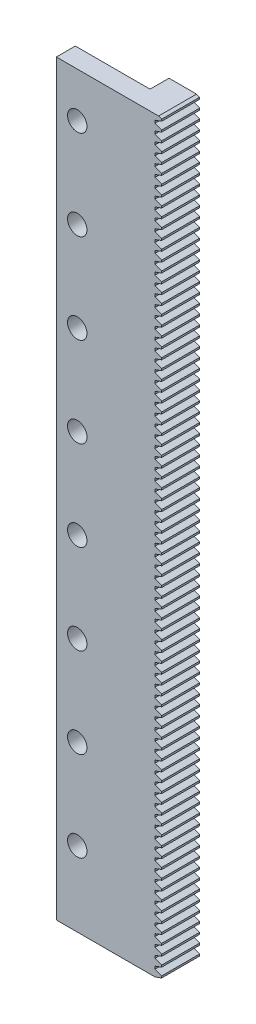
SolidWorks part; units mm, degrees
ref_plane "Front Plane" through (0, 0, 0) normal (0, 0, 1) x (1, 0, 0)
ref_plane "Top Plane" through (0, 0, 0) normal (0, 1, 0) x (1, 0, 0)
ref_plane "Right Plane" through (0, 0, 0) normal (1, 0, 0) x (0, 0, -1)
sketch "Sketch2" plane through (0, 0, 0) normal (0, 0, 1) x (1, 0, 0)
  line L0 (0, -62.5) -> (0, 62.5) construction
  line L1 (-3.5, -62.5) -> (3.5, -62.5) construction
  line L2 (-3.5, -62.5) -> (-3.5, 62.5) construction
  line L3 (-3.5, 62.5) -> (3.5, 62.5) construction
  line L4 (3.5, -62.5) -> (3.5, 62.5) construction
  line L5 (-3.5, -62.5) -> (3.5, 62.5) construction
  line L6 (-3.5, 62.5) -> (3.5, -62.5) construction
  line L202 (3.5, -62.5) -> (-3.5, -62.5)
  line L203 (-3.5, -62.5) -> (-3.5, 62.5)
  line L204 (-3.5, 62.5) -> (13.6024, 62.5)
  line L591 (3.5, -62.5) -> (8, -62.5)
  line L592 (-8, -15) -> (8, -15) construction
  line L593 (-8, -15) -> (-8, 15) construction
  line L594 (-8, 15) -> (8, 15) construction
  line L595 (8, -15) -> (8, 15) construction
  line L596 (-8, -15) -> (8, 15) construction
  line L597 (-8, 15) -> (8, -15) construction
  line L598 (8, -62.5) -> (13, -62.5)
  line L600 (13, -62.5) -> (14.125, -62.0905)
  line L601 (14.125, -62.0905) -> (14.125, -61.7831)
  line L602 (14.125, -61.7831) -> (13, -61.3736)
  line L603 (13, -61.3736) -> (13, -60.9292)
  line L604 (13, -60.9292) -> (14.125, -60.5197)
  line L605 (14.125, -60.5197) -> (14.125, -60.2123)
  line L606 (14.125, -60.2123) -> (13, -59.8028)
  line L607 (13, -59.8028) -> (13, -59.3584)
  line L608 (13, -59.3584) -> (14.125, -58.9489)
  line L609 (14.125, -58.9489) -> (14.125, -58.6415)
  line L610 (14.125, -58.6415) -> (13, -58.232)
  line L611 (13, -58.232) -> (13, -57.7876)
  line L612 (13, -57.7876) -> (14.125, -57.3781)
  line L613 (14.125, -57.3781) -> (14.125, -57.0707)
  line L614 (14.125, -57.0707) -> (13, -56.6613)
  line L615 (13, -56.6613) -> (13, -56.2168)
  line L616 (13, -56.2168) -> (14.125, -55.8073)
  line L617 (14.125, -55.8073) -> (14.125, -55.4999)
  line L618 (14.125, -55.4999) -> (13, -55.0905)
  line L619 (13, -55.0905) -> (13, -54.646)
  line L620 (13, -54.646) -> (14.125, -54.2366)
  line L621 (14.125, -54.2366) -> (14.125, -53.9291)
  line L622 (14.125, -53.9291) -> (13, -53.5197)
  line L623 (13, -53.5197) -> (13, -53.0752)
  line L624 (13, -53.0752) -> (14.125, -52.6658)
  line L625 (14.125, -52.6658) -> (14.125, -52.3583)
  line L626 (14.125, -52.3583) -> (13, -51.9489)
  line L627 (13, -51.9489) -> (13, -51.5044)
  line L628 (13, -51.5044) -> (14.125, -51.095)
  line L629 (14.125, -51.095) -> (14.125, -50.7875)
  line L630 (14.125, -50.7875) -> (13, -50.3781)
  line L631 (13, -50.3781) -> (13, -49.9336)
  line L632 (13, -49.9336) -> (14.125, -49.5242)
  line L633 (14.125, -49.5242) -> (14.125, -49.2167)
  line L634 (14.125, -49.2167) -> (13, -48.8073)
  line L635 (13, -48.8073) -> (13, -48.3628)
  line L636 (13, -48.3628) -> (14.125, -47.9534)
  line L637 (14.125, -47.9534) -> (14.125, -47.6459)
  line L638 (14.125, -47.6459) -> (13, -47.2365)
  line L639 (13, -47.2365) -> (13, -46.792)
  line L640 (13, -46.792) -> (14.125, -46.3826)
  line L641 (14.125, -46.3826) -> (14.125, -46.0751)
  line L642 (14.125, -46.0751) -> (13, -45.6657)
  line L643 (13, -45.6657) -> (13, -45.2212)
  line L644 (13, -45.2212) -> (14.125, -44.8118)
  line L645 (14.125, -44.8118) -> (14.125, -44.5043)
  line L646 (14.125, -44.5043) -> (13, -44.0949)
  line L647 (13, -44.0949) -> (13, -43.6504)
  line L648 (13, -43.6504) -> (14.125, -43.241)
  line L649 (14.125, -43.241) -> (14.125, -42.9335)
  line L650 (14.125, -42.9335) -> (13, -42.5241)
  line L651 (13, -42.5241) -> (13, -42.0796)
  line L652 (13, -42.0796) -> (14.125, -41.6702)
  line L653 (14.125, -41.6702) -> (14.125, -41.3628)
  line L654 (14.125, -41.3628) -> (13, -40.9533)
  line L655 (13, -40.9533) -> (13, -40.5089)
  line L656 (13, -40.5089) -> (14.125, -40.0994)
  line L657 (14.125, -40.0994) -> (14.125, -39.792)
  line L658 (14.125, -39.792) -> (13, -39.3825)
  line L659 (13, -39.3825) -> (13, -38.9381)
  line L660 (13, -38.9381) -> (14.125, -38.5286)
  line L661 (14.125, -38.5286) -> (14.125, -38.2212)
  line L662 (14.125, -38.2212) -> (13, -37.8117)
  line L663 (13, -37.8117) -> (13, -37.3673)
  line L664 (13, -37.3673) -> (14.125, -36.9578)
  line L665 (14.125, -36.9578) -> (14.125, -36.6504)
  line L666 (14.125, -36.6504) -> (13, -36.2409)
  line L667 (13, -36.2409) -> (13, -35.7965)
  line L668 (13, -35.7965) -> (14.125, -35.387)
  line L669 (14.125, -35.387) -> (14.125, -35.0796)
  line L670 (14.125, -35.0796) -> (13, -34.6701)
  line L671 (13, -34.6701) -> (13, -34.2257)
  line L672 (13, -34.2257) -> (14.125, -33.8162)
  line L673 (14.125, -33.8162) -> (14.125, -33.5088)
  line L674 (14.125, -33.5088) -> (13, -33.0993)
  line L675 (13, -33.0993) -> (13, -32.6549)
  line L676 (13, -32.6549) -> (14.125, -32.2454)
  line L677 (14.125, -32.2454) -> (14.125, -31.938)
  line L678 (14.125, -31.938) -> (13, -31.5285)
  line L679 (13, -31.5285) -> (13, -31.0841)
  line L680 (13, -31.0841) -> (14.125, -30.6746)
  line L681 (14.125, -30.6746) -> (14.125, -30.3672)
  line L682 (14.125, -30.3672) -> (13, -29.9577)
  line L683 (13, -29.9577) -> (13, -29.5133)
  line L684 (13, -29.5133) -> (14.125, -29.1038)
  line L685 (14.125, -29.1038) -> (14.125, -28.7964)
  line L686 (14.125, -28.7964) -> (13, -28.3869)
  line L687 (13, -28.3869) -> (13, -27.9425)
  line L688 (13, -27.9425) -> (14.125, -27.533)
  line L689 (14.125, -27.533) -> (14.125, -27.2256)
  line L690 (14.125, -27.2256) -> (13, -26.8161)
  line L691 (13, -26.8161) -> (13, -26.3717)
  line L692 (13, -26.3717) -> (14.125, -25.9622)
  line L693 (14.125, -25.9622) -> (14.125, -25.6548)
  line L694 (14.125, -25.6548) -> (13, -25.2453)
  line L695 (13, -25.2453) -> (13, -24.8009)
  line L696 (13, -24.8009) -> (14.125, -24.3914)
  line L697 (14.125, -24.3914) -> (14.125, -24.084)
  line L698 (14.125, -24.084) -> (13, -23.6745)
  line L699 (13, -23.6745) -> (13, -23.2301)
  line L700 (13, -23.2301) -> (14.125, -22.8206)
  line L701 (14.125, -22.8206) -> (14.125, -22.5132)
  line L702 (14.125, -22.5132) -> (13, -22.1037)
  line L703 (13, -22.1037) -> (13, -21.6593)
  line L704 (13, -21.6593) -> (14.125, -21.2498)
  line L705 (14.125, -21.2498) -> (14.125, -20.9424)
  line L706 (14.125, -20.9424) -> (13, -20.5329)
  line L707 (13, -20.5329) -> (13, -20.0885)
  line L708 (13, -20.0885) -> (14.125, -19.679)
  line L709 (14.125, -19.679) -> (14.125, -19.3716)
  line L710 (14.125, -19.3716) -> (13, -18.9621)
  line L711 (13, -18.9621) -> (13, -18.5177)
  line L712 (13, -18.5177) -> (14.125, -18.1082)
  line L713 (14.125, -18.1082) -> (14.125, -17.8008)
  line L714 (14.125, -17.8008) -> (13, -17.3913)
  line L715 (13, -17.3913) -> (13, -16.9469)
  line L716 (13, -16.9469) -> (14.125, -16.5374)
  line L717 (14.125, -16.5374) -> (14.125, -16.23)
  line L718 (14.125, -16.23) -> (13, -15.8205)
  line L719 (13, -15.8205) -> (13, -15.3761)
  line L720 (13, -15.3761) -> (14.125, -14.9666)
  line L721 (14.125, -14.9666) -> (14.125, -14.6592)
  line L722 (14.125, -14.6592) -> (13, -14.2497)
  line L723 (13, -14.2497) -> (13, -13.8053)
  line L724 (13, -13.8053) -> (14.125, -13.3958)
  line L725 (14.125, -13.3958) -> (14.125, -13.0884)
  line L726 (14.125, -13.0884) -> (13, -12.679)
  line L727 (13, -12.679) -> (13, -12.2345)
  line L728 (13, -12.2345) -> (14.125, -11.8251)
  line L729 (14.125, -11.8251) -> (14.125, -11.5176)
  line L730 (14.125, -11.5176) -> (13, -11.1082)
  line L731 (13, -11.1082) -> (13, -10.6637)
  line L732 (13, -10.6637) -> (14.125, -10.2543)
  line L733 (14.125, -10.2543) -> (14.125, -9.9468)
  line L734 (14.125, -9.9468) -> (13, -9.5374)
  line L735 (13, -9.5374) -> (13, -9.0929)
  line L736 (13, -9.0929) -> (14.125, -8.6835)
  line L737 (14.125, -8.6835) -> (14.125, -8.376)
  line L738 (14.125, -8.376) -> (13, -7.9666)
  line L739 (13, -7.9666) -> (13, -7.5221)
  line L740 (13, -7.5221) -> (14.125, -7.1127)
  line L741 (14.125, -7.1127) -> (14.125, -6.8052)
  line L742 (14.125, -6.8052) -> (13, -6.3958)
  line L743 (13, -6.3958) -> (13, -5.9513)
  line L744 (13, -5.9513) -> (14.125, -5.5419)
  line L745 (14.125, -5.5419) -> (14.125, -5.2344)
  line L746 (14.125, -5.2344) -> (13, -4.825)
  line L747 (13, -4.825) -> (13, -4.3805)
  line L748 (13, -4.3805) -> (14.125, -3.9711)
  line L749 (14.125, -3.9711) -> (14.125, -3.6636)
  line L750 (14.125, -3.6636) -> (13, -3.2542)
  line L751 (13, -3.2542) -> (13, -2.8097)
  line L752 (13, -2.8097) -> (14.125, -2.4003)
  line L753 (14.125, -2.4003) -> (14.125, -2.0928)
  line L754 (14.125, -2.0928) -> (13, -1.6834)
  line L755 (13, -1.6834) -> (13, -1.2389)
  line L756 (13, -1.2389) -> (14.125, -0.8295)
  line L757 (14.125, -0.8295) -> (14.125, -0.522)
  line L758 (14.125, -0.522) -> (13, -0.1126)
  line L759 (13, -0.1126) -> (13, 0.3319)
  line L760 (13, 0.3319) -> (14.125, 0.7413)
  line L761 (14.125, 0.7413) -> (14.125, 1.0487)
  line L762 (14.125, 1.0487) -> (13, 1.4582)
  line L763 (13, 1.4582) -> (13, 1.9026)
  line L764 (13, 1.9026) -> (14.125, 2.3121)
  line L765 (14.125, 2.3121) -> (14.125, 2.6195)
  line L766 (14.125, 2.6195) -> (13, 3.029)
  line L767 (13, 3.029) -> (13, 3.4734)
  line L768 (13, 3.4734) -> (14.125, 3.8829)
  line L769 (14.125, 3.8829) -> (14.125, 4.1903)
  line L770 (14.125, 4.1903) -> (13, 4.5998)
  line L771 (13, 4.5998) -> (13, 5.0442)
  line L772 (13, 5.0442) -> (14.125, 5.4537)
  line L773 (14.125, 5.4537) -> (14.125, 5.7611)
  line L774 (14.125, 5.7611) -> (13, 6.1706)
  line L775 (13, 6.1706) -> (13, 6.615)
  line L776 (13, 6.615) -> (14.125, 7.0245)
  line L777 (14.125, 7.0245) -> (14.125, 7.3319)
  line L778 (14.125, 7.3319) -> (13, 7.7414)
  line L779 (13, 7.7414) -> (13, 8.1858)
  line L780 (13, 8.1858) -> (14.125, 8.5953)
  line L781 (14.125, 8.5953) -> (14.125, 8.9027)
  line L782 (14.125, 8.9027) -> (13, 9.3122)
  line L783 (13, 9.3122) -> (13, 9.7566)
  line L784 (13, 9.7566) -> (14.125, 10.1661)
  line L785 (14.125, 10.1661) -> (14.125, 10.4735)
  line L786 (14.125, 10.4735) -> (13, 10.883)
  line L787 (13, 10.883) -> (13, 11.3274)
  line L788 (13, 11.3274) -> (14.125, 11.7369)
  line L789 (14.125, 11.7369) -> (14.125, 12.0443)
  line L790 (14.125, 12.0443) -> (13, 12.4538)
  line L791 (13, 12.4538) -> (13, 12.8982)
  line L792 (13, 12.8982) -> (14.125, 13.3077)
  line L793 (14.125, 13.3077) -> (14.125, 13.6151)
  line L794 (14.125, 13.6151) -> (13, 14.0246)
  line L795 (13, 14.0246) -> (13, 14.469)
  line L796 (13, 14.469) -> (14.125, 14.8785)
  line L797 (14.125, 14.8785) -> (14.125, 15.1859)
  line L798 (14.125, 15.1859) -> (13, 15.5954)
  line L799 (13, 15.5954) -> (13, 16.0398)
  line L800 (13, 16.0398) -> (14.125, 16.4493)
  line L801 (14.125, 16.4493) -> (14.125, 16.7567)
  line L802 (14.125, 16.7567) -> (13, 17.1662)
  line L803 (13, 17.1662) -> (13, 17.6106)
  line L804 (13, 17.6106) -> (14.125, 18.0201)
  line L805 (14.125, 18.0201) -> (14.125, 18.3275)
  line L806 (14.125, 18.3275) -> (13, 18.737)
  line L807 (13, 18.737) -> (13, 19.1814)
  line L808 (13, 19.1814) -> (14.125, 19.5909)
  line L809 (14.125, 19.5909) -> (14.125, 19.8983)
  line L810 (14.125, 19.8983) -> (13, 20.3078)
  line L811 (13, 20.3078) -> (13, 20.7522)
  line L812 (13, 20.7522) -> (14.125, 21.1617)
  line L813 (14.125, 21.1617) -> (14.125, 21.4691)
  line L814 (14.125, 21.4691) -> (13, 21.8786)
  line L815 (13, 21.8786) -> (13, 22.323)
  line L816 (13, 22.323) -> (14.125, 22.7325)
  line L817 (14.125, 22.7325) -> (14.125, 23.0399)
  line L818 (14.125, 23.0399) -> (13, 23.4494)
  line L819 (13, 23.4494) -> (13, 23.8938)
  line L820 (13, 23.8938) -> (14.125, 24.3033)
  line L821 (14.125, 24.3033) -> (14.125, 24.6107)
  line L822 (14.125, 24.6107) -> (13, 25.0202)
  line L823 (13, 25.0202) -> (13, 25.4646)
  line L824 (13, 25.4646) -> (14.125, 25.8741)
  line L825 (14.125, 25.8741) -> (14.125, 26.1815)
  line L826 (14.125, 26.1815) -> (13, 26.591)
  line L827 (13, 26.591) -> (13, 27.0354)
  line L828 (13, 27.0354) -> (14.125, 27.4449)
  line L829 (14.125, 27.4449) -> (14.125, 27.7523)
  line L830 (14.125, 27.7523) -> (13, 28.1618)
  line L831 (13, 28.1618) -> (13, 28.6062)
  line L832 (13, 28.6062) -> (14.125, 29.0157)
  line L833 (14.125, 29.0157) -> (14.125, 29.3231)
  line L834 (14.125, 29.3231) -> (13, 29.7325)
  line L835 (13, 29.7325) -> (13, 30.177)
  line L836 (13, 30.177) -> (14.125, 30.5864)
  line L837 (14.125, 30.5864) -> (14.125, 30.8939)
  line L838 (14.125, 30.8939) -> (13, 31.3033)
  line L839 (13, 31.3033) -> (13, 31.7478)
  line L840 (13, 31.7478) -> (14.125, 32.1572)
  line L841 (14.125, 32.1572) -> (14.125, 32.4647)
  line L842 (14.125, 32.4647) -> (13, 32.8741)
  line L843 (13, 32.8741) -> (13, 33.3186)
  line L844 (13, 33.3186) -> (14.125, 33.728)
  line L845 (14.125, 33.728) -> (14.125, 34.0355)
  line L846 (14.125, 34.0355) -> (13, 34.4449)
  line L847 (13, 34.4449) -> (13, 34.8894)
  line L848 (13, 34.8894) -> (14.125, 35.2988)
  line L849 (14.125, 35.2988) -> (14.125, 35.6063)
  line L850 (14.125, 35.6063) -> (13, 36.0157)
  line L851 (13, 36.0157) -> (13, 36.4602)
  line L852 (13, 36.4602) -> (14.125, 36.8696)
  line L853 (14.125, 36.8696) -> (14.125, 37.1771)
  line L854 (14.125, 37.1771) -> (13, 37.5865)
  line L855 (13, 37.5865) -> (13, 38.031)
  line L856 (13, 38.031) -> (14.125, 38.4404)
  line L857 (14.125, 38.4404) -> (14.125, 38.7479)
  line L858 (14.125, 38.7479) -> (13, 39.1573)
  line L859 (13, 39.1573) -> (13, 39.6018)
  line L860 (13, 39.6018) -> (14.125, 40.0112)
  line L861 (14.125, 40.0112) -> (14.125, 40.3187)
  line L862 (14.125, 40.3187) -> (13, 40.7281)
  line L863 (13, 40.7281) -> (13, 41.1726)
  line L864 (13, 41.1726) -> (14.125, 41.582)
  line L865 (14.125, 41.582) -> (14.125, 41.8895)
  line L866 (14.125, 41.8895) -> (13, 42.2989)
  line L867 (13, 42.2989) -> (13, 42.7434)
  line L868 (13, 42.7434) -> (14.125, 43.1528)
  line L869 (14.125, 43.1528) -> (14.125, 43.4602)
  line L870 (14.125, 43.4602) -> (13, 43.8697)
  line L871 (13, 43.8697) -> (13, 44.3142)
  line L872 (13, 44.3142) -> (14.125, 44.7236)
  line L873 (14.125, 44.7236) -> (14.125, 45.031)
  line L874 (14.125, 45.031) -> (13, 45.4405)
  line L875 (13, 45.4405) -> (13, 45.8849)
  line L876 (13, 45.8849) -> (14.125, 46.2944)
  line L877 (14.125, 46.2944) -> (14.125, 46.6018)
  line L878 (14.125, 46.6018) -> (13, 47.0113)
  line L879 (13, 47.0113) -> (13, 47.4557)
  line L880 (13, 47.4557) -> (14.125, 47.8652)
  line L881 (14.125, 47.8652) -> (14.125, 48.1726)
  line L882 (14.125, 48.1726) -> (13, 48.5821)
  line L883 (13, 48.5821) -> (13, 49.0265)
  line L884 (13, 49.0265) -> (14.125, 49.436)
  line L885 (14.125, 49.436) -> (14.125, 49.7434)
  line L886 (14.125, 49.7434) -> (13, 50.1529)
  line L887 (13, 50.1529) -> (13, 50.5973)
  line L888 (13, 50.5973) -> (14.125, 51.0068)
  line L889 (14.125, 51.0068) -> (14.125, 51.3142)
  line L890 (14.125, 51.3142) -> (13, 51.7237)
  line L891 (13, 51.7237) -> (13, 52.1681)
  line L892 (13, 52.1681) -> (14.125, 52.5776)
  line L893 (14.125, 52.5776) -> (14.125, 52.885)
  line L894 (14.125, 52.885) -> (13, 53.2945)
  line L895 (13, 53.2945) -> (13, 53.7389)
  line L896 (13, 53.7389) -> (14.125, 54.1484)
  line L897 (14.125, 54.1484) -> (14.125, 54.4558)
  line L898 (14.125, 54.4558) -> (13, 54.8653)
  line L899 (13, 54.8653) -> (13, 55.3097)
  line L900 (13, 55.3097) -> (14.125, 55.7192)
  line L901 (14.125, 55.7192) -> (14.125, 56.0266)
  line L902 (14.125, 56.0266) -> (13, 56.4361)
  line L903 (13, 56.4361) -> (13, 56.8805)
  line L904 (13, 56.8805) -> (14.125, 57.29)
  line L905 (14.125, 57.29) -> (14.125, 57.5974)
  line L906 (14.125, 57.5974) -> (13, 58.0069)
  line L907 (13, 58.0069) -> (13, 58.4513)
  line L908 (13, 58.4513) -> (14.125, 58.8608)
  line L909 (14.125, 58.8608) -> (14.125, 59.1682)
  line L910 (14.125, 59.1682) -> (13, 59.5777)
  line L911 (13, 59.5777) -> (13, 60.0221)
  line L912 (13, 60.0221) -> (14.125, 60.4316)
  line L913 (14.125, 60.4316) -> (14.125, 60.739)
  line L914 (14.125, 60.739) -> (13, 61.1485)
  line L915 (13, 61.1485) -> (13, 61.5929)
  line L916 (13, 61.5929) -> (14.125, 62.0024)
  line L917 (14.125, 62.0024) -> (14.125, 62.3098)
  line L918 (14.125, 62.3098) -> (13, 62.7193)
  line L919 (13, 62.7193) -> (13, 63.1637)
  line L920 (13, 63.1637) -> (14.125, 63.5732)
  line L921 (14.125, 63.5732) -> (14.125, 63.8806)
  line L922 (14.125, 63.8806) -> (13, 64.2901)
  line L923 (13, 64.2901) -> (13, 64.7345)
  line L924 (13, 64.7345) -> (14.125, 65.144)
  line L925 (14.125, 65.144) -> (14.125, 65.4514)
  line L926 (14.125, 65.4514) -> (13, 65.8609)
  line L927 (13, 65.8609) -> (13, 66.3053)
  line L928 (13, 66.3053) -> (14.125, 66.7148)
  line L929 (14.125, 66.7148) -> (14.125, 67.0222)
  line L930 (14.125, 67.0222) -> (13, 67.4317)
  line L931 (13, 67.4317) -> (13, 67.8761)
  line L932 (13, 67.8761) -> (14.125, 68.2856)
  line L933 (14.125, 68.2856) -> (14.125, 68.593)
  line L934 (14.125, 68.593) -> (13, 69.0025)
  line L935 (13, 69.0025) -> (13, 69.4469)
  line L936 (13, 69.4469) -> (14.125, 69.8564)
  line L937 (14.125, 69.8564) -> (14.125, 70.1638)
  line L938 (14.125, 70.1638) -> (13, 70.5733)
  line L939 (13, 70.5733) -> (13, 71.0177)
  line L940 (13, 71.0177) -> (14.125, 71.4272)
  line L941 (14.125, 71.4272) -> (14.125, 71.7346)
  line L942 (14.125, 71.7346) -> (13, 72.144)
  line L943 (13, 72.144) -> (13, 72.5885)
  line L944 (13, 72.5885) -> (14.125, 72.998)
  line L945 (14.125, 72.998) -> (14.125, 73.3054)
  line L946 (14.125, 73.3054) -> (13, 73.7148)
  line L947 (13, 73.7148) -> (13, 74.1593)
  line L948 (13, 74.1593) -> (14.125, 74.5687)
  line L949 (14.125, 74.5687) -> (14.125, 74.8762)
  line L950 (14.125, 74.8762) -> (13, 75.2856)
  line L951 (13, 75.2856) -> (13, 75.7301)
  line L952 (13, 75.7301) -> (14.125, 76.1395)
  line L953 (14.125, 76.1395) -> (14.125, 76.447)
  line L954 (14.125, 76.447) -> (13, 76.8564)
  line L955 (13, 76.8564) -> (13, 77.3009)
  line L956 (13, 77.3009) -> (14.125, 77.7103)
  line L957 (14.125, 77.7103) -> (14.125, 78.0178)
  line L958 (14.125, 78.0178) -> (13, 78.4272)
  line L959 (13, 78.4272) -> (13, 78.8717)
  line L960 (13, 78.8717) -> (14.125, 79.2811)
  line L961 (14.125, 79.2811) -> (14.125, 79.5886)
  line L962 (14.125, 79.5886) -> (13, 79.998)
  line L963 (13, 79.998) -> (13, 80.4425)
  line L964 (13, 80.4425) -> (14.125, 80.8519)
  line L965 (14.125, 80.8519) -> (14.125, 81.1594)
  line L966 (14.125, 81.1594) -> (13, 81.5688)
  line L967 (13, 81.5688) -> (13, 82.0133)
  line L968 (13, 82.0133) -> (14.125, 82.4227)
  line L969 (14.125, 82.4227) -> (14.125, 82.7302)
  line L970 (14.125, 82.7302) -> (13, 83.1396)
  line L971 (13, 83.1396) -> (13, 83.5841)
  line L972 (13, 83.5841) -> (14.125, 83.9935)
  line L973 (14.125, 83.9935) -> (14.125, 84.301)
  line L974 (14.125, 84.301) -> (13, 84.7104)
  line L975 (13, 84.7104) -> (13, 85.1549)
  line L976 (13, 85.1549) -> (14.125, 85.5643)
  line L977 (14.125, 85.5643) -> (14.125, 85.8717)
  line L978 (14.125, 85.8717) -> (13, 86.2812)
  line L979 (13, 86.2812) -> (13, 86.7257)
  line L980 (13, 86.7257) -> (14.125, 87.1351)
  line L981 (14.125, 87.1351) -> (14.125, 87.4425)
  line L982 (14.125, 87.4425) -> (13, 87.852)
  line L983 (13, 87.852) -> (13, 88.2964)
  line L984 (13, 88.2964) -> (14.125, 88.7059)
  line L985 (14.125, 88.7059) -> (14.125, 89.0133)
  line L986 (14.125, 89.0133) -> (13, 89.4228)
  line L987 (13, 89.4228) -> (13, 89.8672)
  line L988 (13, 89.8672) -> (14.125, 90.2767)
  line L989 (14.125, 90.2767) -> (14.125, 90.5841)
  line L990 (14.125, 90.5841) -> (13, 90.9936)
  line L991 (13, 90.9936) -> (13, 91.438)
  line L992 (13, 91.438) -> (14.125, 91.8475)
  line L993 (14.125, 91.8475) -> (14.125, 92.1549)
  line L994 (14.125, 92.1549) -> (13, 92.5644)
  line L995 (13, 92.5644) -> (13, 93.0088)
  line L996 (13, 93.0088) -> (14.125, 93.4183)
  line L997 (14.125, 93.4183) -> (14.125, 93.7257)
  line L998 (14.125, 93.7257) -> (13, 94.1352)
  line L999 (13, 94.1352) -> (13, 94.5796)
  line L1000 (13, 94.5796) -> (14.125, 94.9891)
  line L1001 (14.125, 94.9891) -> (14.125, 95.2965)
  line L1002 (14.125, 95.2965) -> (13, 95.706)
  line L1003 (13, 95.706) -> (13, 96.1504)
  line L1004 (13, 96.1504) -> (14.125, 96.5599)
  line L1005 (14.125, 96.5599) -> (14.125, 96.8673)
  line L1006 (14.125, 96.8673) -> (13, 97.2768)
  line L1007 (13, 97.2768) -> (13, 97.7212)
  line L1008 (13, 97.7212) -> (14.125, 98.1307)
  line L1009 (14.125, 98.1307) -> (14.125, 98.4381)
  line L1010 (14.125, 98.4381) -> (13, 98.8476)
  line L1011 (13, 98.8476) -> (13, 99.292)
  line L1012 (13, 99.292) -> (14.125, 99.7015)
  line L1013 (14.125, 99.7015) -> (14.125, 100.0089)
  line L1014 (14.125, 100.0089) -> (13, 100.4184)
  line L1015 (13, 100.4184) -> (13, 100.8628)
  line L1016 (13, 100.8628) -> (14.125, 101.2723)
  line L1017 (14.125, 101.2723) -> (14.125, 101.5797)
  line L1018 (14.125, 101.5797) -> (13, 101.9892)
  line L1019 (13, 101.9892) -> (13, 102.4336)
  line L1020 (13, 102.4336) -> (14.125, 102.8431)
  line L1021 (14.125, 102.8431) -> (14.125, 103.1505)
  line L1022 (14.125, 103.1505) -> (13, 103.56)
  line L1023 (13, 103.56) -> (13, 104.0044)
  line L1024 (13, 104.0044) -> (14.125, 104.4139)
  line L1025 (14.125, 104.4139) -> (14.125, 104.7213)
  line L1026 (14.125, 104.7213) -> (13, 105.1308)
  line L1027 (13, 105.1308) -> (13, 105.5752)
  line L1028 (13, 105.5752) -> (14.125, 105.9847)
  line L1029 (14.125, 105.9847) -> (14.125, 106.2921)
  line L1030 (14.125, 106.2921) -> (13, 106.7016)
  line L1031 (13, 106.7016) -> (13, 107.146)
  line L1032 (13, 107.146) -> (14.125, 107.5555)
  line L1033 (14.125, 107.5555) -> (14.125, 107.8629)
  line L1034 (14.125, 107.8629) -> (13, 108.2724)
  line L1035 (13, 108.2724) -> (13, 108.7168)
  line L1036 (13, 108.7168) -> (14.125, 109.1263)
  line L1037 (14.125, 109.1263) -> (14.125, 109.4337)
  line L1038 (14.125, 109.4337) -> (13, 109.8432)
  line L1039 (13, 109.8432) -> (13, 110.2876)
  line L1040 (13, 110.2876) -> (14.125, 110.6971)
  line L1041 (14.125, 110.6971) -> (14.125, 111.0045)
  line L1042 (14.125, 111.0045) -> (13, 111.414)
  line L1043 (13, 111.414) -> (13, 111.8584)
  line L1044 (13, 111.8584) -> (14.125, 112.2679)
  line L1045 (14.125, 112.2679) -> (14.125, 112.5753)
  line L1046 (14.125, 112.5753) -> (13, 112.9848)
  line L1047 (13, 112.9848) -> (13, 113.4292)
  line L1048 (13, 113.4292) -> (14.125, 113.8387)
  line L1049 (14.125, 113.8387) -> (14.125, 114.1461)
  line L1050 (14.125, 114.1461) -> (13, 114.5555)
  line L1051 (13, 114.5555) -> (13, 115)
  line L1052 (13, 115) -> (14.125, 115.4095)
  line L1053 (14.125, 115.4095) -> (14.125, 115.7169)
  line L1054 (14.125, 115.7169) -> (13, 116.1263)
  line L1055 (13, 116.1263) -> (13, 116.5708)
  line L1056 (13, 116.5708) -> (14.125, 116.9802)
  line L1057 (14.125, 116.9802) -> (14.125, 117.2877)
  line L1058 (14.125, 117.2877) -> (13, 117.6971)
  line L1059 (13, 117.6971) -> (13, 118.1416)
  line L1060 (13, 118.1416) -> (14.125, 118.551)
  line L1061 (14.125, 118.551) -> (14.125, 118.8585)
  line L1062 (14.125, 118.8585) -> (13, 119.2679)
  line L1063 (13, 119.2679) -> (13, 119.7124)
  line L1064 (13, 119.7124) -> (14.125, 120.1218)
  line L1065 (14.125, 120.1218) -> (14.125, 120.4293)
  line L1066 (14.125, 120.4293) -> (13, 120.8387)
  line L1067 (13, 120.8387) -> (13, 121.2832)
  line L1068 (13, 121.2832) -> (14.125, 121.6926)
  line L1069 (14.125, 121.6926) -> (14.125, 122.0001)
  line L1070 (14.125, 122.0001) -> (13, 122.4095)
  line L1071 (13, 122.4095) -> (13, 122.854)
  line L1072 (13, 122.854) -> (14.125, 123.2634)
  line L1073 (14.125, 123.2634) -> (14.125, 123.5709)
  line L1074 (14.125, 123.5709) -> (13, 123.9803)
  line L1075 (13, 123.9803) -> (13, 124.4248)
  line L1076 (13, 124.4248) -> (14.125, 124.8342)
  line L1077 (14.125, 124.8342) -> (14.125, 125.1417)
  line L1078 (14.125, 125.1417) -> (13, 125.5511)
  line L1079 (13, 125.5511) -> (13, 125.9956)
  line L1080 (13, 125.9956) -> (14.125, 126.405)
  line L1081 (14.125, 126.405) -> (14.125, 126.7125)
  line L1082 (14.125, 126.7125) -> (13, 127.1219)
  line L1083 (13, 127.1219) -> (13, 127.5664)
  line L1084 (13, 127.5664) -> (14.125, 127.9758)
  line L1085 (14.125, 127.9758) -> (14.125, 128.2832)
  line L1086 (14.125, 128.2832) -> (13, 128.6927)
  line L1087 (13, 128.6927) -> (13, 129.1372)
  line L1088 (13, 129.1372) -> (14.125, 129.5466)
  line L1089 (14.125, 129.5466) -> (14.125, 129.854)
  line L1090 (14.125, 129.854) -> (13, 130.2635)
  line L1091 (13, 130.2635) -> (13, 130.7079)
  line L1092 (13, 130.7079) -> (14.125, 131.1174)
  line L1093 (14.125, 131.1174) -> (14.125, 131.4248)
  line L1094 (14.125, 131.4248) -> (13, 131.8343)
  line L1095 (13, 131.8343) -> (13, 132.2787)
  line L1096 (13, 132.2787) -> (14.125, 132.6882)
  line L1097 (14.125, 132.6882) -> (14.125, 132.9956)
  line L1098 (14.125, 132.9956) -> (13, 133.4051)
  line L1099 (13, 133.4051) -> (13, 133.8495)
  line L1100 (13, 133.8495) -> (14.125, 134.259)
  line L1101 (14.125, 134.259) -> (14.125, 134.5664)
  line L1102 (14.125, 134.5664) -> (13, 134.9759)
  line L1103 (13, 134.9759) -> (13, 135.4203)
  line L1104 (13, 135.4203) -> (14.125, 135.8298)
  line L1105 (14.125, 135.8298) -> (14.125, 136.1372)
  line L1106 (14.125, 136.1372) -> (13, 136.5467)
  line L1107 (13, 136.5467) -> (13, 136.9911)
  line L1108 (13, 136.9911) -> (14.125, 137.4006)
  line L1109 (14.125, 137.4006) -> (14.125, 137.708)
  line L1110 (14.125, 137.708) -> (13, 138.1175)
  line L1111 (13, 138.1175) -> (13, 138.5619)
  line L1112 (13, 138.5619) -> (14.125, 138.9714)
  line L1113 (14.125, 138.9714) -> (14.125, 139.2788)
  line L1114 (14.125, 139.2788) -> (13, 139.6883)
  line L1115 (13, 139.6883) -> (13, 140.1327)
  line L1116 (13, 140.1327) -> (14.125, 140.5422)
  line L1117 (14.125, 140.5422) -> (14.125, 140.8496)
  line L1118 (14.125, 140.8496) -> (13, 141.2591)
  line L1119 (13, 141.2591) -> (13, 141.7035)
  line L1120 (13, 141.7035) -> (14.125, 142.113)
  line L1121 (14.125, 142.113) -> (14.125, 142.4204)
  line L1122 (14.125, 142.4204) -> (13, 142.8299)
  line L1123 (13, 142.8299) -> (13, 143.2743)
  line L1124 (13, 143.2743) -> (14.125, 143.6838)
  line L1125 (14.125, 143.6838) -> (14.125, 143.9912)
  line L1126 (14.125, 143.9912) -> (13, 144.4007)
  line L1127 (13, 144.4007) -> (13, 144.8451)
  line L1128 (13, 144.8451) -> (14.125, 145.2546)
  line L1129 (14.125, 145.2546) -> (14.125, 145.562)
  line L1130 (14.125, 145.562) -> (13, 145.9715)
  line L1131 (13, 145.9715) -> (13, 146.4159)
  line L1132 (13, 146.4159) -> (14.125, 146.8254)
  line L1133 (14.125, 146.8254) -> (14.125, 147.1328)
  line L1134 (14.125, 147.1328) -> (13, 147.5423)
  line L1135 (13, 147.5423) -> (13, 147.9867)
  line L1136 (13, 147.9867) -> (14.125, 148.3962)
  line L1137 (14.125, 148.3962) -> (14.125, 148.7036)
  line L1138 (14.125, 148.7036) -> (13, 149.1131)
  line L1139 (13, 149.1131) -> (13, 149.5575)
  line L1140 (13, 149.5575) -> (14.125, 149.967)
  line L1141 (14.125, 149.967) -> (14.125, 150.2744)
  line L1142 (14.125, 150.2744) -> (13, 150.6839)
  line L1143 (13, 150.6839) -> (13, 151.1283)
  line L1144 (13, 151.1283) -> (14.125, 151.5378)
  line L1145 (14.125, 151.5378) -> (14.125, 151.8452)
  line L1146 (14.125, 151.8452) -> (13, 152.2547)
  line L1147 (13, 152.2547) -> (13, 152.6991)
  line L1148 (13, 152.6991) -> (14.125, 153.1086)
  line L1149 (14.125, 153.1086) -> (14.125, 153.416)
  line L1150 (14.125, 153.416) -> (13, 153.8255)
  line L1151 (13, 153.8255) -> (13, 154.2699)
  line L1152 (13, 154.2699) -> (14.125, 154.6794)
  line L1153 (14.125, 154.6794) -> (14.125, 154.9868)
  line L1154 (14.125, 154.9868) -> (13, 155.3963)
  line L1155 (13, 155.3963) -> (13, 155.8407)
  line L1156 (13, 155.8407) -> (14.125, 156.2502)
  line L1157 (14.125, 156.2502) -> (14.125, 156.5576)
  line L1158 (14.125, 156.5576) -> (13, 156.9671)
  line L1159 (13, 156.9671) -> (13, 157.4115)
  line L1160 (13, 157.4115) -> (14.125, 157.821)
  line L1161 (14.125, 157.821) -> (14.125, 158.1284)
  line L1162 (14.125, 158.1284) -> (13, 158.5378)
  line L1163 (13, 158.5378) -> (13, 158.9823)
  line L1164 (13, 158.9823) -> (14.125, 159.3917)
  line L1165 (14.125, 159.3917) -> (14.125, 159.6992)
  line L1166 (14.125, 159.6992) -> (13, 160.1086)
  line L1167 (13, 160.1086) -> (13, 160.5531)
  line L1168 (13, 160.5531) -> (14.125, 160.9625)
  line L1169 (14.125, 160.9625) -> (14.125, 161.27)
  line L1170 (14.125, 161.27) -> (13, 161.6794)
  line L1171 (13, 161.6794) -> (13, 162.1239)
  line L1172 (13, 162.1239) -> (14.125, 162.5333)
  line L1173 (14.125, 162.5333) -> (14.125, 162.8408)
  line L1174 (14.125, 162.8408) -> (13, 163.2502)
  line L1175 (13, 163.2502) -> (13, 163.6947)
  line L1176 (13, 163.6947) -> (14.125, 164.1041)
  line L1177 (14.125, 164.1041) -> (14.125, 164.4116)
  line L1178 (14.125, 164.4116) -> (13, 164.821)
  line L1179 (13, 164.821) -> (13, 165.2655)
  line L1180 (13, 165.2655) -> (14.125, 165.6749)
  line L1181 (14.125, 165.6749) -> (14.125, 165.9824)
  line L1182 (14.125, 165.9824) -> (13, 166.3918)
  line L1183 (13, 166.3918) -> (13, 166.8363)
  line L1184 (13, 166.8363) -> (14.125, 167.2457)
  line L1185 (14.125, 167.2457) -> (14.125, 167.5532)
  line L1186 (14.125, 167.5532) -> (13, 167.9626)
  line L1187 (13, 167.9626) -> (13, 168.4071)
  line L1188 (13, 168.4071) -> (14.125, 168.8165)
  line L1189 (14.125, 168.8165) -> (14.125, 169.124)
  line L1190 (14.125, 169.124) -> (13, 169.5334)
  line L1191 (13, 169.5334) -> (13, 169.9779)
  line L1192 (13, 169.9779) -> (14.125, 170.3873)
  line L1193 (14.125, 170.3873) -> (14.125, 170.6948)
  line L1194 (14.125, 170.6948) -> (13, 171.1042)
  line L1195 (13, 171.1042) -> (13, 171.5487)
  line L1196 (13, 171.5487) -> (14.125, 171.9581)
  line L1197 (14.125, 171.9581) -> (14.125, 172.2655)
  line L1198 (14.125, 172.2655) -> (13, 172.675)
  line L1199 (13, 172.675) -> (13, 173.1194)
  line L1200 (13, 173.1194) -> (14.125, 173.5289)
  line L1201 (14.125, 173.5289) -> (14.125, 173.8363)
  line L1202 (14.125, 173.8363) -> (13, 174.2458)
  line L1203 (13, 174.2458) -> (13, 174.6902)
  line L1204 (13, 174.6902) -> (14.125, 175.0997)
  line L1205 (14.125, 175.0997) -> (14.125, 175.4071)
  line L1206 (14.125, 175.4071) -> (13, 175.8166)
  line L1207 (13, 175.8166) -> (13, 176.261)
  line L1208 (13, 176.261) -> (14.125, 176.6705)
  line L1209 (14.125, 176.6705) -> (14.125, 176.9779)
  line L1210 (14.125, 176.9779) -> (13, 177.3874)
  line L1211 (13, 177.3874) -> (13, 177.8318)
  line L1212 (13, 177.8318) -> (14.125, 178.2413)
  line L1213 (14.125, 178.2413) -> (14.125, 178.5487)
  line L1214 (14.125, 178.5487) -> (13, 178.9582)
  line L1215 (13, 178.9582) -> (13, 179.4026)
  line L1216 (13, 179.4026) -> (14.125, 179.8121)
  line L1217 (14.125, 179.8121) -> (14.125, 180.1195)
  line L1218 (14.125, 180.1195) -> (13, 180.529)
  line L1219 (13, 180.529) -> (13, 180.9734)
  line L1220 (13, 180.9734) -> (14.125, 181.3829)
  line L1221 (14.125, 181.3829) -> (14.125, 181.6903)
  line L1222 (14.125, 181.6903) -> (13, 182.0998)
  line L1223 (13, 182.0998) -> (13, 182.5442)
  line L1224 (13, 182.5442) -> (14.125, 182.9537)
  line L1225 (14.125, 182.9537) -> (14.125, 183.2611)
  line L1226 (14.125, 183.2611) -> (13, 183.6706)
  line L1227 (13, 183.6706) -> (13, 184.115)
  line L1228 (13, 184.115) -> (14.125, 184.5245)
  line L1229 (14.125, 184.5245) -> (14.125, 184.8319)
  line L1230 (14.125, 184.8319) -> (13, 185.2414)
  line L1231 (13, 185.2414) -> (13, 185.6858)
  line L1232 (13, 185.6858) -> (14.125, 186.0953)
  line L1233 (14.125, 186.0953) -> (14.125, 186.4027)
  line L1234 (14.125, 186.4027) -> (13, 186.8122)
  line L1235 (13, 186.8122) -> (13, 187.2566)
  line L1236 (13, 187.2566) -> (14.125, 187.6661)
  line L1237 (14.125, 187.6661) -> (14.125, 187.9735)
  line L1238 (14.125, 187.9735) -> (13, 188.383)
  line L1239 (13, 188.383) -> (13, 188.8274)
  line L1240 (13, 188.8274) -> (14.125, 189.2369)
  line L1241 (14.125, 189.2369) -> (14.125, 189.5443)
  line L1242 (14.125, 189.5443) -> (13, 189.9538)
  line L1243 (13, 189.9538) -> (13, 190.3982)
  line L1244 (13, 190.3982) -> (14.125, 190.8077)
  line L1245 (14.125, 190.8077) -> (14.125, 191.1151)
  line L1246 (14.125, 191.1151) -> (13, 191.5246)
  line L1247 (13, 191.5246) -> (13, 191.969)
  line L1248 (13, 191.969) -> (14.125, 192.3785)
  line L1249 (14.125, 192.3785) -> (14.125, 192.6859)
  line L1250 (14.125, 192.6859) -> (13, 193.0954)
  line L1251 (13, 193.0954) -> (13, 193.5398)
  line L1252 (13, 193.5398) -> (14.125, 193.9493)
  line L1253 (14.125, 193.9493) -> (14.125, 194.2567)
  line L1254 (14.125, 194.2567) -> (13, 194.6662)
  line L1255 (13, 194.6662) -> (13, 195.1106)
  line L1256 (13, 195.1106) -> (14.125, 195.5201)
  line L1257 (14.125, 195.5201) -> (14.125, 195.8275)
  line L1258 (14.125, 195.8275) -> (13, 196.237)
  line L1259 (13, 196.237) -> (13, 196.6814)
  line L1260 (13, 196.6814) -> (14.125, 197.0909)
  line L1261 (14.125, 197.0909) -> (14.125, 197.3983)
  line L1262 (14.125, 197.3983) -> (13, 197.8078)
  line L1263 (13, 197.8078) -> (13, 198.2522)
  line L1264 (13, 198.2522) -> (14.125, 198.6617)
  line L1265 (14.125, 198.6617) -> (14.125, 198.9691)
  line L1266 (14.125, 198.9691) -> (13, 199.3786)
  line L1267 (13, 199.3786) -> (13, 199.823)
  line L1268 (13, 199.823) -> (14.125, 200.2325)
  line L1269 (14.125, 200.2325) -> (14.125, 200.5399)
  line L1270 (14.125, 200.5399) -> (13, 200.9493)
  line L1271 (13, 200.9493) -> (13, 201.3938)
  line L1272 (13, 201.3938) -> (14.125, 201.8032)
  line L1273 (14.125, 201.8032) -> (14.125, 202.1107)
  line L1274 (14.125, 202.1107) -> (13, 202.5201)
  line L1275 (13, 202.5201) -> (13, 202.9646)
  line L1276 (13, 202.9646) -> (14.125, 203.374)
  line L1277 (14.125, 203.374) -> (14.125, 203.6815)
  line L1278 (14.125, 203.6815) -> (13, 204.0909)
  line L1279 (13, 204.0909) -> (13, 204.5354)
  line L1280 (13, 204.5354) -> (14.125, 204.9448)
  line L1281 (14.125, 204.9448) -> (14.125, 205.2523)
  line L1282 (14.125, 205.2523) -> (13, 205.6617)
  line L1283 (13, 205.6617) -> (13, 206.1062)
  line L1284 (13, 206.1062) -> (14.125, 206.5156)
  line L1285 (14.125, 206.5156) -> (14.125, 206.8231)
  line L1286 (14.125, 206.8231) -> (13, 207.2325)
  line L1287 (13, 207.2325) -> (13, 207.677)
  line L1288 (13, 207.677) -> (14.125, 208.0864)
  line L1289 (14.125, 208.0864) -> (14.125, 208.3939)
  line L1290 (14.125, 208.3939) -> (13, 208.8033)
  line L1291 (13, 208.8033) -> (13, 209.2478)
  line L1292 (13, 209.2478) -> (14.125, 209.6572)
  line L1293 (14.125, 209.6572) -> (14.125, 209.9647)
  line L1294 (14.125, 209.9647) -> (13, 210.3741)
  line L1295 (13, 210.3741) -> (13, 210.8186)
  line L1296 (13, 210.8186) -> (14.125, 211.228)
  line L1297 (14.125, 211.228) -> (14.125, 211.5355)
  line L1298 (14.125, 211.5355) -> (13, 211.9449)
  line L1299 (13, 211.9449) -> (13, 212.3894)
  line L1300 (13, 212.3894) -> (14.125, 212.7988)
  line L1301 (14.125, 212.7988) -> (14.125, 213.1063)
  line L1302 (14.125, 213.1063) -> (13, 213.5157)
  line L1303 (13, 213.5157) -> (13, 213.9602)
  line L1304 (13, 213.9602) -> (14.125, 214.3696)
  line L1305 (14.125, 214.3696) -> (14.125, 214.677)
  line L1306 (14.125, 214.677) -> (13, 215.0865)
  line L1307 (13, 215.0865) -> (13, 215.5309)
  line L1308 (13, 215.5309) -> (14.125, 215.9404)
  line L1309 (14.125, 215.9404) -> (14.125, 216.2478)
  line L1310 (14.125, 216.2478) -> (13, 216.6573)
  line L1311 (13, 216.6573) -> (13, 217.1017)
  line L1312 (13, 217.1017) -> (14.125, 217.5112)
  line L1313 (14.125, 217.5112) -> (14.125, 217.8186)
  line L1314 (14.125, 217.8186) -> (13, 218.2281)
  line L1315 (13, 218.2281) -> (13, 218.6725)
  line L1316 (13, 218.6725) -> (14.125, 219.082)
  line L1317 (14.125, 219.082) -> (14.125, 219.3894)
  line L1318 (14.125, 219.3894) -> (13, 219.7989)
  line L1319 (13, 219.7989) -> (13, 220.2433)
  line L1320 (13, 220.2433) -> (14.125, 220.6528)
  line L1321 (14.125, 220.6528) -> (14.125, 220.9602)
  line L1322 (14.125, 220.9602) -> (13, 221.3697)
  line L1323 (13, 221.3697) -> (13, 221.8141)
  line L1324 (13, 221.8141) -> (14.125, 222.2236)
  line L1325 (14.125, 222.2236) -> (14.125, 222.531)
  line L1326 (14.125, 222.531) -> (13, 222.9405)
  line L1327 (13, 222.9405) -> (13, 223.3849)
  line L1328 (13, 223.3849) -> (14.125, 223.7944)
  line L1329 (14.125, 223.7944) -> (14.125, 224.1018)
  line L1330 (14.125, 224.1018) -> (13, 224.5113)
  line L1331 (13, 224.5113) -> (13, 224.9557)
  line L1332 (13, 224.9557) -> (14.125, 225.3652)
  line L1333 (14.125, 225.3652) -> (14.125, 225.6726)
  line L1334 (14.125, 225.6726) -> (13, 226.0821)
  line L1335 (13, 226.0821) -> (13, 226.5265)
  line L1336 (13, 226.5265) -> (14.125, 226.936)
  line L1337 (14.125, 226.936) -> (14.125, 227.2434)
  line L1338 (14.125, 227.2434) -> (13, 227.6529)
  line L1339 (13, 227.6529) -> (13, 228.0973)
  line L1340 (13, 228.0973) -> (14.125, 228.5068)
  line L1341 (14.125, 228.5068) -> (14.125, 228.8142)
  line L1342 (14.125, 228.8142) -> (13, 229.2237)
  line L1343 (13, 229.2237) -> (13, 229.6681)
  line L1344 (13, 229.6681) -> (14.125, 230.0776)
  line L1345 (14.125, 230.0776) -> (14.125, 230.385)
  line L1346 (14.125, 230.385) -> (13, 230.7945)
  line L1347 (13, 230.7945) -> (13, 231.2389)
  line L1348 (13, 231.2389) -> (14.125, 231.6484)
  line L1349 (14.125, 231.6484) -> (14.125, 231.9558)
  line L1350 (14.125, 231.9558) -> (13, 232.3653)
  line L1351 (13, 232.3653) -> (13, 232.8097)
  line L1352 (13, 232.8097) -> (14.125, 233.2192)
  line L1353 (14.125, 233.2192) -> (14.125, 233.5266)
  line L1354 (14.125, 233.5266) -> (13, 233.9361)
  line L1355 (13, 233.9361) -> (13, 234.3805)
  line L1356 (13, 234.3805) -> (14.125, 234.79)
  line L1357 (14.125, 234.79) -> (14.125, 235.0974)
  line L1358 (14.125, 235.0974) -> (13, 235.5069)
  line L1359 (13, 235.5069) -> (13, 235.9513)
  line L1360 (13, 235.9513) -> (14.125, 236.3608)
  line L1361 (14.125, 236.3608) -> (14.125, 236.6682)
  line L1362 (14.125, 236.6682) -> (13, 237.0777)
  line L1363 (13, 237.0777) -> (13, 237.2999)
  line L1369 (9, 0) -> (9, -62.5)
  line L1370 (9, 0) -> (9, 62.5)
  circle A1 centre (0, 55) radius 1.1
  circle A2 centre (0, 40) radius 1.1
  circle A3 centre (0, 25) radius 1.1
  circle A4 centre (0, 10) radius 1.1
  circle A5 centre (0, -5) radius 1.1
  circle A6 centre (0, -20) radius 1.1
  circle A7 centre (0, -35) radius 1.1
  circle A8 centre (0, -50) radius 1.1
  circle A9 centre (0, 55) radius 1.625
  circle A10 centre (0, 40) radius 1.625
  circle A11 centre (0, 25) radius 1.625
  circle A12 centre (0, 10) radius 1.625
  circle A13 centre (0, -5) radius 1.625
  circle A14 centre (0, -20) radius 1.625
  circle A15 centre (0, -35) radius 1.625
  circle A16 centre (0, -50) radius 1.625
  point P0 (0, 0)
  point P26 (0, 0)
  dimension "D3" = 2.2
  dimension "D7" = 3.25
  dimension "D1" = 7
  dimension "D2" = 125
  dimension "D4" = 7.5
  dimension "D6" = 15
  dimension "D9" = 16
  dimension "D10" = 30
  dimension "D11" = 5
  dimension "D12" = 12.5
  dimension "D5" = 8
  dimension "D8" = 8
extrude "Boss-Extrude1" add sketch "Sketch2" along normal blind 6.35 contours L204 L203 L202 L593 | L598 L600 L601 L602 L603 L604 L605 L606 L607 L608 L609 L610 L611 L612 L613 L614 L615 L616 L617 L618 L619 L620 L621 L622 L623 L624 L625 L626 L627 L628 L629 L630 L631 L632 L633 L634 L635 L636 L637 L638 L639 L640 L641 L642 L643 L644 L645 L646 L647 region at (2.872, -0.1109, 0) region at (11.2804, 0.0052, 0)
extrude "Cut-Extrude1" cut sketch "Sketch2<3>" along normal blind 3.175 contours L204 L203 L202 L591 A16 A15 A14 A13 A12 A11 A10 A9 | A9 A1 | A11 A3 | A12 A4 | A14 A6 | A15 A7 | A10 A2 | A13 A5 | A16 A8 region at (2.872, -0.1109, 0) region at (-1.579, 55, 0) region at (-1.579, 40, 0) region at (-1.579, 25, 0) region at (-1.579, 10, 0) region at (-1.579, -5, 0) region at (-1.579, -20, 0) region at (-1.579, -35, 0) region at (-1.579, -50, 0)
sketch "Sketch2<3>" plane through (0, 0, 0) normal (0, 0, 1) x (1, 0, 0) same geometry as "Sketch2"
